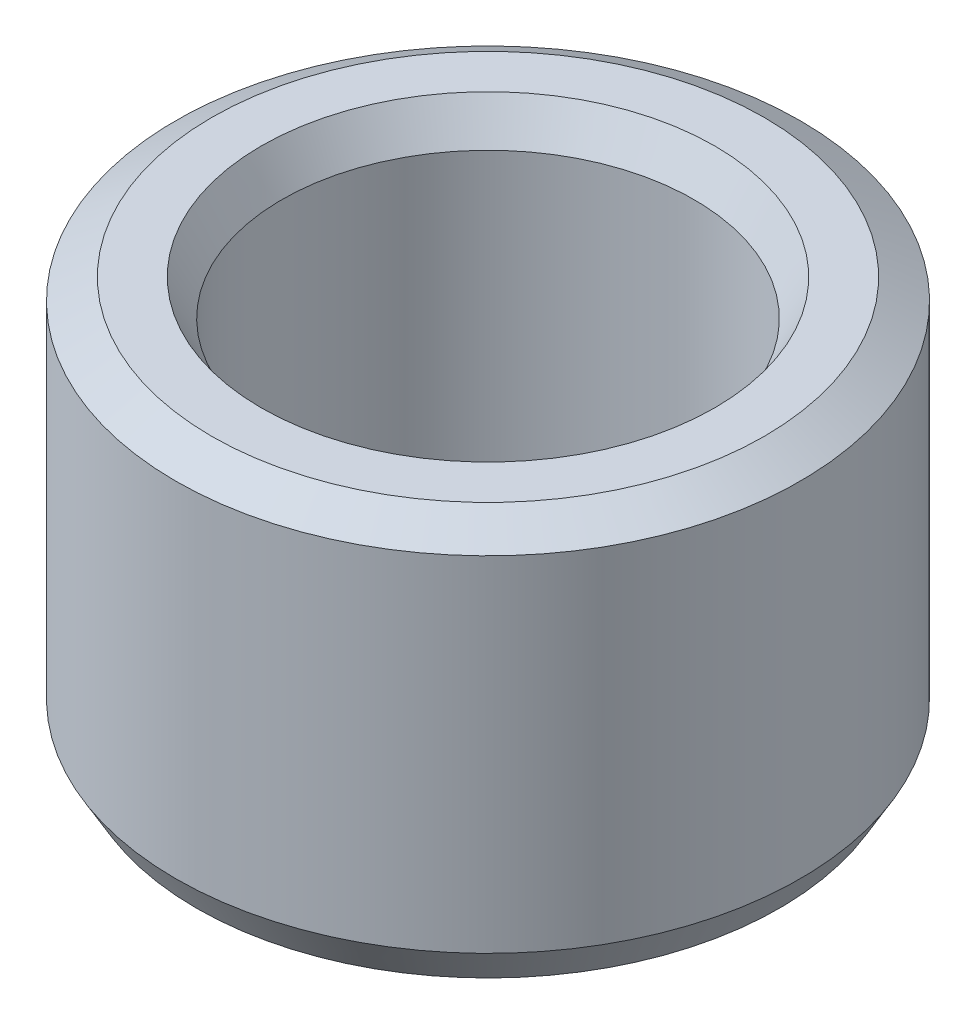
SolidWorks part; units mm, degrees
ref_plane "Front Plane" through (0, 0, 0) normal (0, 0, 1) x (1, 0, 0)
ref_plane "Top Plane" through (0, 0, 0) normal (0, 1, 0) x (1, 0, 0)
ref_plane "Right Plane" through (0, 0, 0) normal (1, 0, 0) x (0, 0, -1)
sketch "Sketch1" plane through (0, 0, 0) normal (0, 1, 0) x (1, 0, 0)
  circle A0 centre (0, 0) radius 10
  dimension "SLEEVE_OD" = 20
extrude "Boss-Extrude1" add sketch "Sketch1" along normal blind 12.846
sketch "Sketch2" plane through (0, 0, 0) normal (0, 1, 0) x (1, 0, 0)
  circle A0 centre (0, 0) radius 6.5986
  dimension "BORE_D" = 13.1971
extrude "Cut-Extrude1" cut sketch "Sketch2" along normal through all
chamfer "Chamfer1" distance 0.6656 angle 60 4 edges at (0, 12.846, 6.5986) (0, 0, 6.5986) (0, 0, 10) (0, 12.846, 10) first distance on face at (0, 12.846, 6.5986) first distance on face at (0, 0, 6.5986) first distance on face at (0, 12.846, 10)
